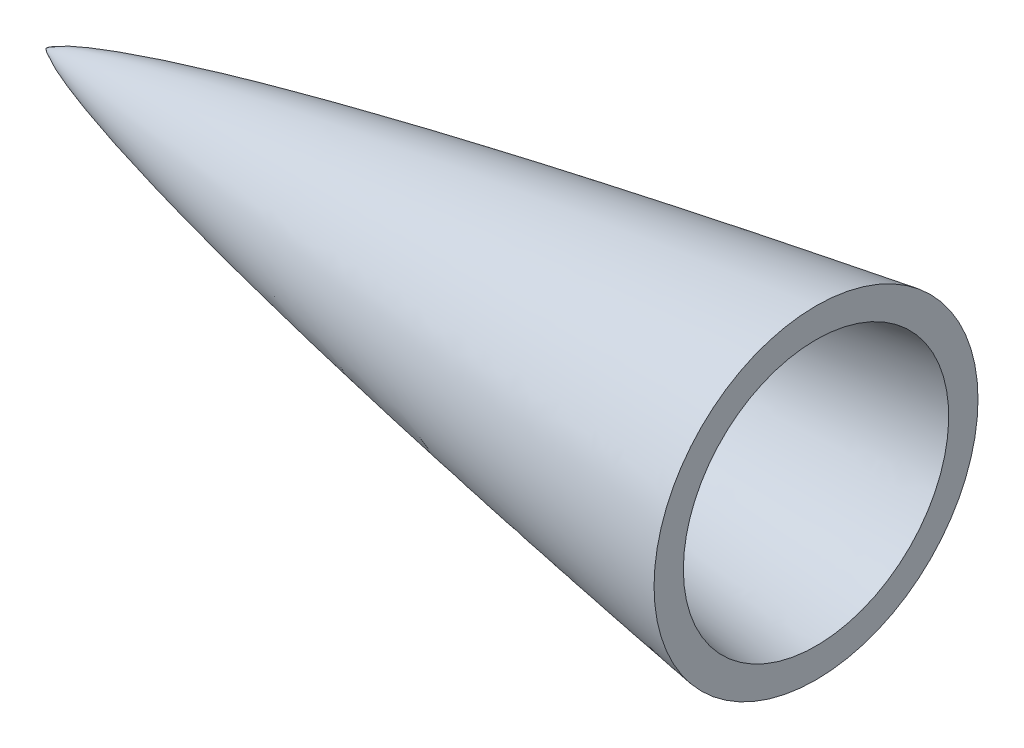
SolidWorks part; units mm, degrees
material "Alloy Steel"
ref_plane "Front Plane" through (0, 0, 0) normal (0, 0, 1) x (1, 0, 0)
ref_plane "Top Plane" through (0, 0, 0) normal (0, 1, 0) x (1, 0, 0)
ref_plane "Right Plane" through (0, 0, 0) normal (1, 0, 0) x (0, 0, -1)
sketch "Sketch1" plane through (0, 0, 0) normal (0, 0, 1) x (1, 0, 0)
  line L0 (0, 0) -> (596.9, 0)
  line L2 (596.9, 0) -> (596.9, 52.7482)
  spline S0 degree 4 poles (0, 0) (0.0024, 0.0056) (0.008, 0.0163) (0.0233, 0.0353) (0.0583, 0.069) (0.1105, 0.1106) (0.1804, 0.1587) (0.2798, 0.2202) (0.3991, 0.287) (0.5391, 0.3592) (0.6997, 0.4363) (0.9322, 0.5415) (1.293, 0.6933) (1.9132, 0.9318) (3.0286, 1.3168) (5.0297, 1.9288) (8.7193, 2.9162) (15.6155, 4.5123) (27.7821, 6.9272) (48.0381, 10.379) (75.5616, 14.4184) (108.703, 18.7111) (145.1674, 22.9502) (181.6719, 26.826) (218.2071, 30.3992) (254.767, 33.7085) (291.348, 36.7768) (327.9472, 39.6184) (364.5629, 42.24) (401.1936, 44.6421) (437.8384, 46.8187) (474.4967, 48.7564) (506.5841, 50.2205) (534.0958, 51.2823) (556.2771, 51.9856) (571.2063, 52.3703) (583.4683, 52.6116) (591.1434, 52.712) (594.9811, 52.744) (596.9, 52.7482) knots 0 0 0 0 0 0.00004 0.000081 0.000162 0.000323 0.000485 0.000646 0.00094 0.001234 0.001534 0.001834 0.002641 0.003843 0.005963 0.009698 0.016588 0.029299 0.05314 0.092371 0.153547 0.214723 0.275899 0.337075 0.398251 0.459427 0.520603 0.581779 0.642954 0.70413 0.765306 0.826482 0.887658 0.918246 0.948834 0.974417 0.987208 1 1 1 1 1 construction
  spline S1 degree 4 poles (0, 0) (0.0024, 0.0056) (0.008, 0.0163) (0.0233, 0.0353) (0.0583, 0.069) (0.1105, 0.1106) (0.1804, 0.1587) (0.2798, 0.2202) (0.3991, 0.287) (0.5391, 0.3592) (0.6997, 0.4363) (0.9322, 0.5415) (1.293, 0.6933) (1.9132, 0.9318) (3.0286, 1.3168) (5.0297, 1.9288) (8.7193, 2.9162) (15.6155, 4.5123) (27.7821, 6.9272) (48.0381, 10.379) (75.5616, 14.4184) (108.703, 18.7111) (145.1674, 22.9502) (181.6719, 26.826) (218.2071, 30.3992) (254.767, 33.7085) (291.348, 36.7768) (327.9472, 39.6184) (364.5629, 42.24) (401.1936, 44.6421) (437.8384, 46.8187) (474.4967, 48.7564) (506.5841, 50.2205) (534.0958, 51.2823) (556.2771, 51.9856) (571.2063, 52.3703) (583.4683, 52.6116) (591.1434, 52.712) (594.9811, 52.744) (596.9, 52.7482) knots 0 0 0 0 0 0.00004 0.000081 0.000162 0.000323 0.000485 0.000646 0.00094 0.001234 0.001534 0.001834 0.002641 0.003843 0.005963 0.009698 0.016588 0.029299 0.05314 0.092371 0.153547 0.214723 0.275899 0.337075 0.398251 0.459427 0.520603 0.581779 0.642954 0.70413 0.765306 0.826482 0.887658 0.918246 0.948834 0.974417 0.987208 1 1 1 1 1
  dimension "D1" = 596.9
revolve "Revolve1" add sketch "Sketch1" angle 360 about L0
shell "Shell1" thickness 1.9101 removed face at (596.9, 0, 52.7482)
ref_plane "Plane1" through (558.8, 0, 0) normal (1, 0, 0) x (0, 0, -1)
sketch "Sketch2" plane through (558.8, 0, 0) normal (1, 0, 0) x (0, 0, -1)
  circle A0 centre (0, 0) radius 49.2506
  circle A1 centre (0, 0) radius 50.8381
  circle A2 centre (0, 0) radius 50.8381
  dimension "D2" = 1.5875
  dimension "D1" = 0
extrude "Boss-Extrude1" add sketch "Sketch2" along normal blind 76.2
ref_plane "Tip Cut Plane" through (50.8, 0, 0) normal (1, 0, 0) x (0, 0, -1)
sketch "Sketch3" plane through (50.8, 0, 0) normal (1, 0, 0) x (0, 0, -1)
  circle A0 centre (0, 0) radius 53.975
  dimension "D1" = 107.95
extrude "Cut-Extrude1" cut sketch "Sketch3" along normal blind 609.6
sketch "Sketch4" plane through (0, 0, 0) normal (0, 0, 1) x (1, 0, 0)
  line L0 (0, 0) -> (76.2, 0) construction
  dimension "D1" = 76.2
